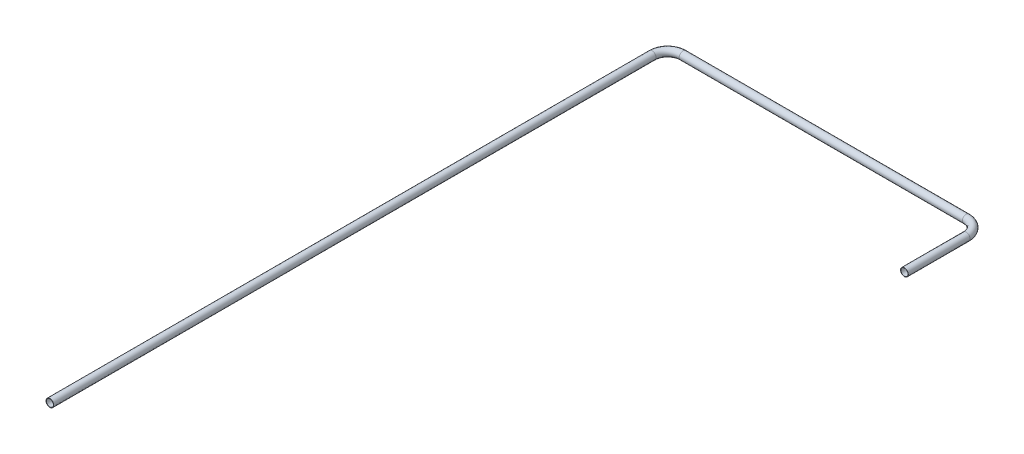
SolidWorks part; units mm, degrees
ref_plane "Front" through (0, 0, 0) normal (0, 0, 1) x (1, 0, 0)
ref_plane "Top" through (0, 0, 0) normal (0, 1, 0) x (1, 0, 0)
ref_plane "Right" through (0, 0, 0) normal (1, 0, 0) x (0, 0, -1)
sketch "Sketch13" plane through (0, 0, 0) normal (0, 1, 0) x (1, 0, 0)
  line L0 (-152.4, 0) -> (-2946.4, 0)
  line L1 (-3098.8, -152.4) -> (-3098.8, -6096)
  line L2 (0, -152.4) -> (0, -762)
  arc A0 (-3098.8, -152.4) -> (-2946.4, 0) centre (-2946.4, -152.4) cw
  arc A1 (0, -152.4) -> (-152.4, 0) centre (-152.4, -152.4) ccw
  point P7 (-3098.8, 0)
  point P10 (0, 0)
  dimension "D3" = 1399794
  dimension "D1" = 6096
  dimension "D2" = 762
  dimension "D4" = 2794
ref_plane "Plane1" through (0, 0, 762) normal (0, 0, 1) x (1, 0, 0)
sketch "Sketch14" plane through (0, 0, 762) normal (0, 0, 1) x (1, 0, 0)
  line L0 (0, 34.925) -> (0, 38.1) construction
  circle A0 centre (0, 0) radius 38.1
  circle A1 centre (0, 0) radius 34.925
  dimension "D1" = 76.2
  dimension "D2" = 3.175
sweep "Sweep1" add profiles "Sketch14" path "Sketch13"
sketch "Sketch15" plane through (0, 0, 0) normal (0, 1, 0) x (1, 0, 0)
  line L0 (0, -762) -> (0, -787.4)
  line L1 (-38.1, -762) -> (38.1, -762) construction
  line L2 (50.8, -838.2) -> (2501.9, -838.2)
  arc A0 (0, -787.4) -> (50.8, -838.2) centre (50.8, -787.4) ccw
  dimension "D1" = 50.8
  dimension "D2" = 25.4
  dimension "D3" = 2451.1
sketch "Sketch16" plane through (0, 0, 762) normal (0, 0, 1) x (1, 0, 0)
  circle A0 centre (0, 0) radius 34.925 construction
  circle A1 centre (0, 0) radius 38.1
  circle A2 centre (0, 0) radius 38.1
  circle A3 centre (0, 0) radius 34.925
  dimension "D1" = 0
sketch "Sketch17" plane through (0, 0, 0) normal (0, 1, 0) x (1, 0, 0)
  line L0 (0, -762) -> (0, -787.4)
  line L1 (-38.1, -762) -> (38.1, -762) construction
  line L2 (50.8, -838.2) -> (914.4, -838.2)
  line L3 (965.2, -889) -> (965.2, -939.8)
  line L4 (1016, -990.6) -> (1117.6, -990.6)
  line L5 (1168.4, -939.8) -> (1168.4, -889)
  line L6 (50.8, -838.2) -> (2501.9, -838.2) construction
  line L7 (1219.2, -838.2) -> (2501.9, -838.2)
  arc A0 (0, -787.4) -> (50.8, -838.2) centre (50.8, -787.4) ccw
  arc A1 (965.2, -889) -> (914.4, -838.2) centre (914.4, -889) ccw
  arc A2 (1016, -990.6) -> (965.2, -939.8) centre (1016, -939.8) cw
  arc A3 (1168.4, -939.8) -> (1117.6, -990.6) centre (1117.6, -939.8) cw
  arc A4 (1219.2, -838.2) -> (1168.4, -889) centre (1219.2, -889) ccw
  point P17 (965.2, -838.2)
  point P20 (965.2, -990.6)
  point P23 (1168.4, -990.6)
  point P26 (1168.4, -838.2)
  dimension "D3" = 50.8
  dimension "D6" = 50.8
  dimension "D7" = 50.8
  dimension "D8" = 50.8
  dimension "D9" = 50.8
  dimension "D1" = 914.4
  dimension "D2" = 25.4
  dimension "D4" = 152.4
  dimension "D5" = 203.2
sketch "Sketch18" plane through (0, 0, 762) normal (0, 0, 1) x (1, 0, 0)
  circle A2 centre (0, 0) radius 38.1
  circle A3 centre (0, 0) radius 34.925
sweep "Sweep3" [suppressed] add profiles "Sketch18" path "Sketch17"
